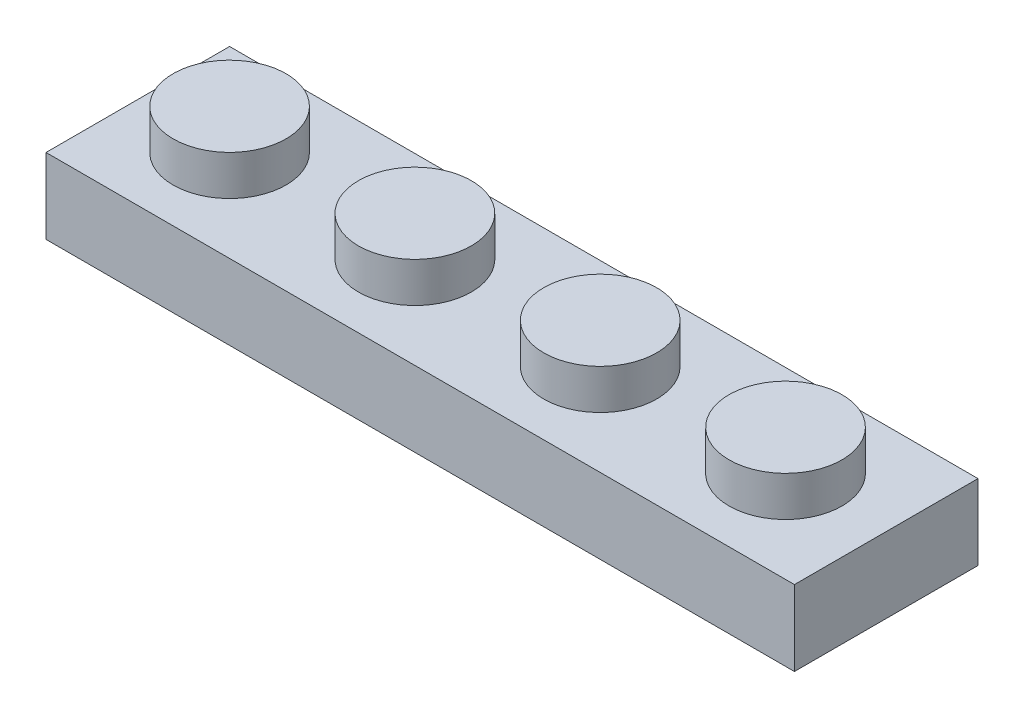
SolidWorks part; units mm, degrees
ref_plane "Спереди" through (0, 0, 0) normal (0, 0, 1) x (1, 0, 0)
ref_plane "Сверху" through (0, 0, 0) normal (0, 1, 0) x (1, 0, 0)
ref_plane "Справа" through (0, 0, 0) normal (1, 0, 0) x (0, 0, -1)
sketch "Эскиз1" plane through (0, 0, 0) normal (0, 1, 0) x (1, 0, 0)
  line L1 (15.9, -3.9) -> (-15.9, -3.9)
  line L2 (15.9, -3.9) -> (15.9, 3.9)
  line L3 (15.9, 3.9) -> (-15.9, 3.9)
  line L4 (-15.9, -3.9) -> (-15.9, 3.9)
  line L5 (15.9, -3.9) -> (-15.9, 3.9) construction
  line L6 (15.9, 3.9) -> (-15.9, -3.9) construction
  point P0 (0, 0)
  dimension "D1" = 31.8
  dimension "D2" = 7.8
extrude "Бобышка-Вытянуть1" add sketch "Эскиз1" along normal blind 3.2
sketch "Эскиз2" plane through (0, 3.2, 0) normal (0, 1, 0) x (1, 0, 0)
  line L0 (-15.9, 3.9) -> (-15.9, -3.9) construction
  line L1 (-15.9, -3.9) -> (15.9, -3.9) construction
  circle A0 centre (-12, 0) radius 2.4
  circle A1 centre (-4.126, 0) radius 2.4
  circle A2 centre (3.748, 0) radius 2.4
  circle A3 centre (11.622, 0) radius 2.4
  dimension "D1" = 3.9
  dimension "D2" = 3.9
  dimension "D3" = 4
extrude "Бобышка-Вытянуть2" add sketch "Эскиз2" along normal blind 1.7
sketch "Эскиз3" plane through (0, 0, 0) normal (0, -1, 0) x (1, 0, 0)
  line L0 (-15.9, -3.9) -> (-15.9, 3.9) construction
  circle A0 centre (-12, 0) radius 2.5
  circle A1 centre (-4.126, 0) radius 2.5
  circle A2 centre (3.748, 0) radius 2.5
  circle A3 centre (11.622, 0) radius 2.5
  dimension "D1" = 3.9
  dimension "D2" = 4
extrude "Вырез-Вытянуть1" cut sketch "Эскиз3" against normal blind 1.8
